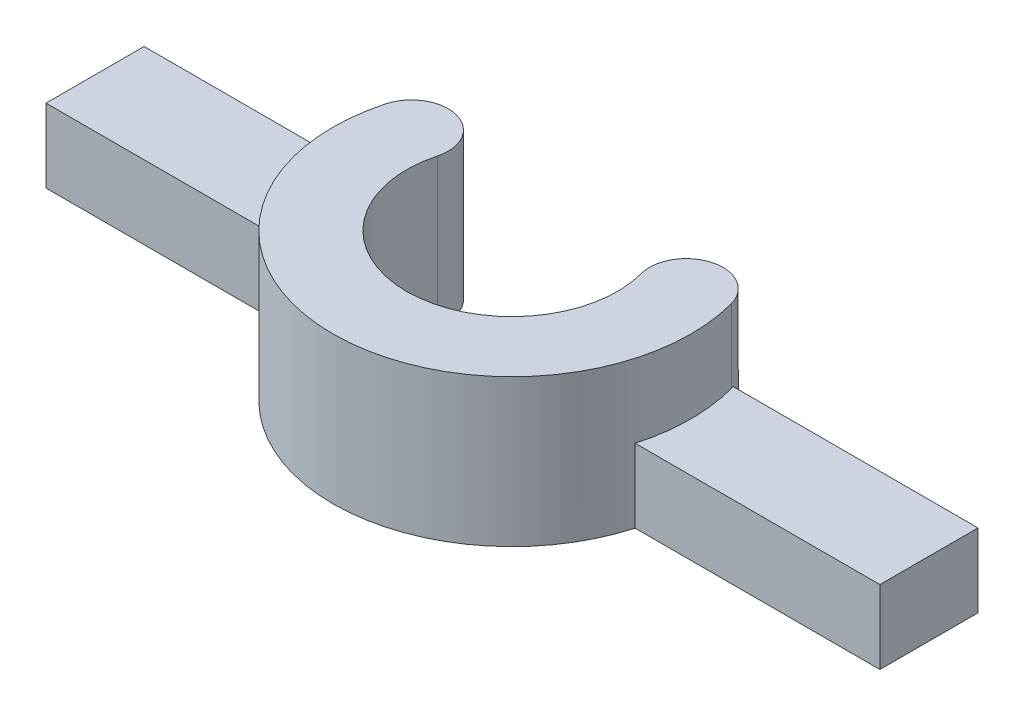
SolidWorks part; units mm, degrees
ref_plane "Front" through (0, 0, 0) normal (0, 0, 1) x (1, 0, 0)
ref_plane "Top" through (0, 0, 0) normal (0, 1, 0) x (1, 0, 0)
ref_plane "Right" through (0, 0, 0) normal (1, 0, 0) x (0, 0, -1)
sketch "Sketch1" plane through (0, 0, 0) normal (0, 1, 0) x (1, 0, 0)
  line L1 (15, -15) -> (-15, -15)
  line L2 (15, -15) -> (15, 15)
  line L3 (15, 15) -> (-15, 15)
  line L4 (-15, -15) -> (-15, 15)
  line L5 (0, 15) -> (0, -15) construction
  line L6 (15, 0) -> (-15, 0) construction
  point P0 (0, 0)
  dimension "D1" = 30
  dimension "D2" = 30
extrude "Boss-Extrude1" add sketch "Sketch1" along normal blind 5
sketch "Sketch2" plane through (0, 5, 0) normal (0, 1, 0) x (1, 0, 0)
  line L1 (5, -5) -> (-5, -5)
  line L2 (5, -5) -> (5, 5)
  line L3 (5, 5) -> (-5, 5)
  line L4 (-5, -5) -> (-5, 5)
  line L5 (0, 5) -> (0, -5) construction
  line L6 (5, 0) -> (-5, 0) construction
  point P0 (0, 0)
  dimension "D1" = 10
  dimension "D2" = 10
extrude "Boss-Extrude2" add sketch "Sketch2" along normal blind 50
sketch "Sketch3" plane through (0, 0, 0) normal (0, 0, 1) x (1, 0, 0)
  line L1 (-5, 55) -> (-15, 55)
  line L2 (-5, 55) -> (-5, 50)
  line L3 (-5, 50) -> (-15, 50)
  line L4 (-15, 55) -> (-15, 50)
  line L5 (-15, 50) -> (-10, 50)
  line L6 (-15, 50) -> (-15, 65)
  line L7 (-15, 65) -> (-10, 65)
  line L8 (-10, 50) -> (-10, 65)
  line L9 (-15, 65) -> (0, 65)
  line L10 (-15, 65) -> (-15, 62)
  line L11 (-15, 62) -> (0, 62)
  line L12 (0, 65) -> (0, 62)
  dimension "D1" = 5
  dimension "D2" = 10
  dimension "D3" = 5
  dimension "D4" = 15
  dimension "D5" = 3
extrude "Boss-Extrude3" add sketch "Sketch3" along normal blind 2 and the other way blind 2 contours L12 L9 L8 L11 | L6 L11 L8 L7 | L11 L6 L1 L8 | L3 L8 L1 L4 | L8 L3 L2 L1
mirror "Mirror1" about plane through (0, 0, 0) normal (1, 0, 0) of "Boss-Extrude3"
sketch "Sketch4" plane through (0, 65, 0) normal (0, 1, 0) x (1, 0, 0)
  circle A0 centre (0, 0) radius 4.3
  circle A1 centre (0, 0) radius 7.3
  dimension "D1" = 8.6
  dimension "D2" = 14.6
extrude "Boss-Extrude4" add sketch "Sketch4" against normal blind 5 and the other way blind 3
sketch "Sketch6" plane through (0, 65, 0) normal (0, 1, 0) x (1, 0, 0)
  line L0 (0, 0) -> (0, 7.3)
  line L1 (-6.322, 3.65) -> (0, 0)
  line L2 (6.322, 3.65) -> (0, 0)
  circle A0 centre (0, 0) radius 4.3
  arc A2 (6.322, 3.65) -> (-6.322, 3.65) centre (0, 0) ccw
extrude "Cut-Extrude1" cut sketch "Sketch6" against normal blind 5 and the other way blind 6
fillet "Fillet1" radius 1.5 2 edges at (6.322, 64, -3.65) (3.7239, 64, -2.15)
fillet "Fillet2" radius 1.5 2 edges at (-3.7239, 64, -2.15) (-6.322, 64, -3.65)
fillet "Fillet3" radius 2 4 edges at (15, 0, 0) (0, 0, 15) (-15, 0, 0) (0, 0, -15)
sketch "Sketch7" plane through (0, 62, 0) normal (0, -1, 0) x (1, 0, 0)
  line L1 (-18.7092, 17.8009) -> (20.7297, 17.8009)
  line L2 (-18.7092, 17.8009) -> (-18.7092, -18.733)
  line L3 (-18.7092, -18.733) -> (20.7297, -18.733)
  line L4 (20.7297, 17.8009) -> (20.7297, -18.733)
extrude "Cut-Extrude2" cut sketch "Sketch7" along normal blind 80
sketch "Sketch8" plane through (-15, 0, 0) normal (-1, 0, 0) x (0, 0, 1)
  line L1 (2, 65) -> (-2, 65)
  line L2 (2, 65) -> (2, 62)
  line L3 (2, 62) -> (-2, 62)
  line L4 (-2, 65) -> (-2, 62)
extrude "Boss-Extrude5" add sketch "Sketch8" along normal blind 2
mirror "Mirror3" about plane through (0, 0, 0) normal (1, 0, 0) of "Boss-Extrude5"
